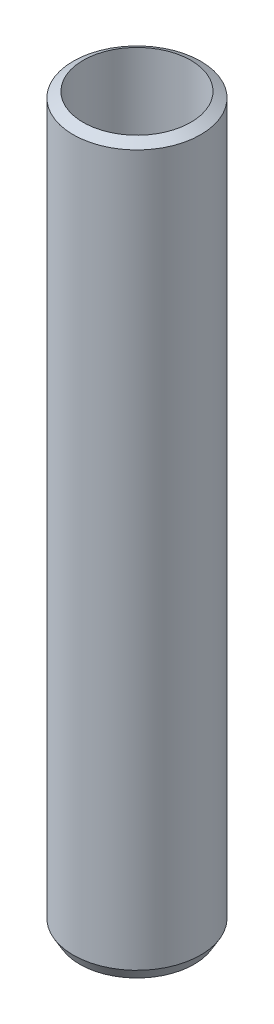
SolidWorks part; units mm, degrees
ref_plane "Front Plane" through (0, 0, 0) normal (0, 0, 1) x (1, 0, 0)
ref_plane "Top Plane" through (0, 0, 0) normal (0, 1, 0) x (1, 0, 0)
ref_plane "Right Plane" through (0, 0, 0) normal (1, 0, 0) x (0, 0, -1)
sketch "Sketch1" plane through (0, 0, 0) normal (0, 1, 0) x (1, 0, 0)
  circle A0 centre (0, 0) radius 52.5
  dimension "SHAFT_OD" = 105
extrude "Boss-Extrude1" add sketch "Sketch1" along normal blind 600
sketch "Sketch2" plane through (0, 0, 0) normal (0, 1, 0) x (1, 0, 0)
  circle A0 centre (0, 0) radius 44.3341
  dimension "BORE_D" = 88.6682
extrude "Cut-Extrude1" cut sketch "Sketch2" along normal through all
chamfer "Chamfer1" distance 5.3626 angle 60 2 edges at (0, 600, 52.5) (0, 0, 52.5) first distance on face at (0, 600, 52.5) first distance on face at (0, 0, 44.3341)
